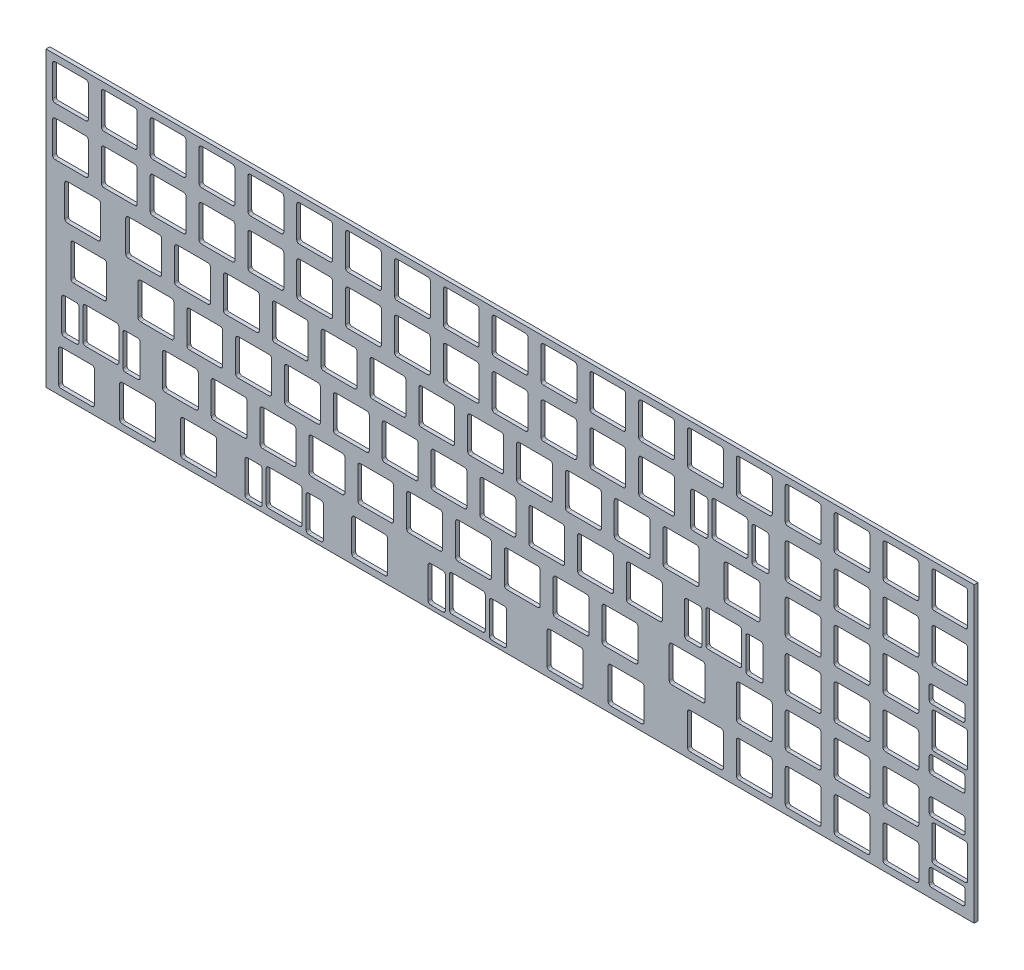
SolidWorks part; units mm, degrees
ref_plane "Front Plane" through (0, 0, 0) normal (0, 0, 1) x (1, 0, 0)
ref_plane "Top Plane" through (0, 0, 0) normal (0, 1, 0) x (1, 0, 0)
ref_plane "Right Plane" through (0, 0, 0) normal (1, 0, 0) x (0, 0, -1)
sketch "Model" plane through (0, 0, 0) normal (0, 0, 1) x (1, 0, 0)
  line L0 (3.525, -2.525) -> (15.525, -2.525)
  line L1 (3.525, -16.525) -> (15.525, -16.525)
  line L2 (2.525, -3.525) -> (2.525, -15.525)
  line L3 (16.525, -3.525) -> (16.525, -15.525)
  line L4 (22.575, -2.525) -> (34.575, -2.525)
  line L5 (22.575, -16.525) -> (34.575, -16.525)
  line L6 (21.575, -3.525) -> (21.575, -15.525)
  line L7 (35.575, -3.525) -> (35.575, -15.525)
  line L8 (41.625, -2.525) -> (53.625, -2.525)
  line L9 (41.625, -16.525) -> (53.625, -16.525)
  line L10 (40.625, -3.525) -> (40.625, -15.525)
  line L11 (54.625, -3.525) -> (54.625, -15.525)
  line L12 (60.675, -2.525) -> (72.675, -2.525)
  line L13 (60.675, -16.525) -> (72.675, -16.525)
  line L14 (59.675, -3.525) -> (59.675, -15.525)
  line L15 (73.675, -3.525) -> (73.675, -15.525)
  line L16 (79.725, -2.525) -> (91.725, -2.525)
  line L17 (79.725, -16.525) -> (91.725, -16.525)
  line L18 (78.725, -3.525) -> (78.725, -15.525)
  line L19 (92.725, -3.525) -> (92.725, -15.525)
  line L20 (98.775, -2.525) -> (110.775, -2.525)
  line L21 (98.775, -16.525) -> (110.775, -16.525)
  line L22 (97.775, -3.525) -> (97.775, -15.525)
  line L23 (111.775, -3.525) -> (111.775, -15.525)
  line L24 (117.825, -2.525) -> (129.825, -2.525)
  line L25 (117.825, -16.525) -> (129.825, -16.525)
  line L26 (116.825, -3.525) -> (116.825, -15.525)
  line L27 (130.825, -3.525) -> (130.825, -15.525)
  line L28 (136.875, -2.525) -> (148.875, -2.525)
  line L29 (136.875, -16.525) -> (148.875, -16.525)
  line L30 (135.875, -3.525) -> (135.875, -15.525)
  line L31 (149.875, -3.525) -> (149.875, -15.525)
  line L32 (155.925, -2.525) -> (167.925, -2.525)
  line L33 (155.925, -16.525) -> (167.925, -16.525)
  line L34 (154.925, -3.525) -> (154.925, -15.525)
  line L35 (168.925, -3.525) -> (168.925, -15.525)
  line L36 (174.975, -2.525) -> (186.975, -2.525)
  line L37 (174.975, -16.525) -> (186.975, -16.525)
  line L38 (173.975, -3.525) -> (173.975, -15.525)
  line L39 (187.975, -3.525) -> (187.975, -15.525)
  line L40 (194.025, -2.525) -> (206.025, -2.525)
  line L41 (194.025, -16.525) -> (206.025, -16.525)
  line L42 (193.025, -3.525) -> (193.025, -15.525)
  line L43 (207.025, -3.525) -> (207.025, -15.525)
  line L44 (213.075, -2.525) -> (225.075, -2.525)
  line L45 (213.075, -16.525) -> (225.075, -16.525)
  line L46 (212.075, -3.525) -> (212.075, -15.525)
  line L47 (226.075, -3.525) -> (226.075, -15.525)
  line L48 (232.125, -2.525) -> (244.125, -2.525)
  line L49 (232.125, -16.525) -> (244.125, -16.525)
  line L50 (231.125, -3.525) -> (231.125, -15.525)
  line L51 (245.125, -3.525) -> (245.125, -15.525)
  line L52 (251.175, -2.525) -> (263.175, -2.525)
  line L53 (251.175, -16.525) -> (263.175, -16.525)
  line L54 (250.175, -3.525) -> (250.175, -15.525)
  line L55 (264.175, -3.525) -> (264.175, -15.525)
  line L56 (270.225, -2.525) -> (282.225, -2.525)
  line L57 (270.225, -16.525) -> (282.225, -16.525)
  line L58 (269.225, -3.525) -> (269.225, -15.525)
  line L59 (283.225, -3.525) -> (283.225, -15.525)
  line L60 (289.275, -2.525) -> (301.275, -2.525)
  line L61 (289.275, -16.525) -> (301.275, -16.525)
  line L62 (288.275, -3.525) -> (288.275, -15.525)
  line L63 (302.275, -3.525) -> (302.275, -15.525)
  line L64 (308.325, -2.525) -> (320.325, -2.525)
  line L65 (308.325, -16.525) -> (320.325, -16.525)
  line L66 (307.325, -3.525) -> (307.325, -15.525)
  line L67 (321.325, -3.525) -> (321.325, -15.525)
  line L68 (327.375, -2.525) -> (339.375, -2.525)
  line L69 (327.375, -16.525) -> (339.375, -16.525)
  line L70 (326.375, -3.525) -> (326.375, -15.525)
  line L71 (340.375, -3.525) -> (340.375, -15.525)
  line L72 (346.425, -2.525) -> (358.425, -2.525)
  line L73 (346.425, -16.525) -> (358.425, -16.525)
  line L74 (345.425, -3.525) -> (345.425, -15.525)
  line L75 (359.425, -3.525) -> (359.425, -15.525)
  line L76 (3.525, -21.575) -> (15.525, -21.575)
  line L77 (3.525, -35.575) -> (15.525, -35.575)
  line L78 (2.525, -22.575) -> (2.525, -34.575)
  line L79 (16.525, -22.575) -> (16.525, -34.575)
  line L80 (22.575, -21.575) -> (34.575, -21.575)
  line L81 (22.575, -35.575) -> (34.575, -35.575)
  line L82 (21.575, -22.575) -> (21.575, -34.575)
  line L83 (35.575, -22.575) -> (35.575, -34.575)
  line L84 (41.625, -21.575) -> (53.625, -21.575)
  line L85 (41.625, -35.575) -> (53.625, -35.575)
  line L86 (40.625, -22.575) -> (40.625, -34.575)
  line L87 (54.625, -22.575) -> (54.625, -34.575)
  line L88 (60.675, -21.575) -> (72.675, -21.575)
  line L89 (60.675, -35.575) -> (72.675, -35.575)
  line L90 (59.675, -22.575) -> (59.675, -34.575)
  line L91 (73.675, -22.575) -> (73.675, -34.575)
  line L92 (79.725, -21.575) -> (91.725, -21.575)
  line L93 (79.725, -35.575) -> (91.725, -35.575)
  line L94 (78.725, -22.575) -> (78.725, -34.575)
  line L95 (92.725, -22.575) -> (92.725, -34.575)
  line L96 (98.775, -21.575) -> (110.775, -21.575)
  line L97 (98.775, -35.575) -> (110.775, -35.575)
  line L98 (97.775, -22.575) -> (97.775, -34.575)
  line L99 (111.775, -22.575) -> (111.775, -34.575)
  line L100 (117.825, -21.575) -> (129.825, -21.575)
  line L101 (117.825, -35.575) -> (129.825, -35.575)
  line L102 (116.825, -22.575) -> (116.825, -34.575)
  line L103 (130.825, -22.575) -> (130.825, -34.575)
  line L104 (136.875, -21.575) -> (148.875, -21.575)
  line L105 (136.875, -35.575) -> (148.875, -35.575)
  line L106 (135.875, -22.575) -> (135.875, -34.575)
  line L107 (149.875, -22.575) -> (149.875, -34.575)
  line L108 (155.925, -21.575) -> (167.925, -21.575)
  line L109 (155.925, -35.575) -> (167.925, -35.575)
  line L110 (154.925, -22.575) -> (154.925, -34.575)
  line L111 (168.925, -22.575) -> (168.925, -34.575)
  line L112 (174.975, -21.575) -> (186.975, -21.575)
  line L113 (174.975, -35.575) -> (186.975, -35.575)
  line L114 (173.975, -22.575) -> (173.975, -34.575)
  line L115 (187.975, -22.575) -> (187.975, -34.575)
  line L116 (194.025, -21.575) -> (206.025, -21.575)
  line L117 (194.025, -35.575) -> (206.025, -35.575)
  line L118 (193.025, -22.575) -> (193.025, -34.575)
  line L119 (207.025, -22.575) -> (207.025, -34.575)
  line L120 (213.075, -21.575) -> (225.075, -21.575)
  line L121 (213.075, -35.575) -> (225.075, -35.575)
  line L122 (212.075, -22.575) -> (212.075, -34.575)
  line L123 (226.075, -22.575) -> (226.075, -34.575)
  line L124 (232.125, -21.575) -> (244.125, -21.575)
  line L125 (232.125, -35.575) -> (244.125, -35.575)
  line L126 (231.125, -22.575) -> (231.125, -34.575)
  line L127 (245.125, -22.575) -> (245.125, -34.575)
  line L128 (260.7, -21.575) -> (272.7, -21.575)
  line L129 (260.7, -35.575) -> (272.7, -35.575)
  line L130 (259.7, -22.575) -> (259.7, -34.575)
  line L131 (273.7, -22.575) -> (273.7, -34.575)
  line L132 (276.263, -22.575) -> (281.013, -22.575)
  line L133 (276.263, -36.575) -> (281.013, -36.575)
  line L134 (275.263, -23.575) -> (275.263, -35.575)
  line L135 (282.013, -23.575) -> (282.013, -35.575)
  line L136 (252.387, -22.575) -> (257.137, -22.575)
  line L137 (252.387, -36.575) -> (257.137, -36.575)
  line L138 (251.387, -23.575) -> (251.387, -35.575)
  line L139 (258.137, -23.575) -> (258.137, -35.575)
  line L140 (289.275, -21.575) -> (301.275, -21.575)
  line L141 (289.275, -35.575) -> (301.275, -35.575)
  line L142 (288.275, -22.575) -> (288.275, -34.575)
  line L143 (302.275, -22.575) -> (302.275, -34.575)
  line L144 (308.325, -21.575) -> (320.325, -21.575)
  line L145 (308.325, -35.575) -> (320.325, -35.575)
  line L146 (307.325, -22.575) -> (307.325, -34.575)
  line L147 (321.325, -22.575) -> (321.325, -34.575)
  line L148 (327.375, -21.575) -> (339.375, -21.575)
  line L149 (327.375, -35.575) -> (339.375, -35.575)
  line L150 (326.375, -22.575) -> (326.375, -34.575)
  line L151 (340.375, -22.575) -> (340.375, -34.575)
  line L152 (346.425, -21.575) -> (358.425, -21.575)
  line L153 (346.425, -35.575) -> (358.425, -35.575)
  line L154 (345.425, -22.575) -> (345.425, -34.575)
  line L155 (359.425, -22.575) -> (359.425, -34.575)
  line L156 (8.2875, -40.625) -> (20.2875, -40.625)
  line L157 (8.2875, -54.625) -> (20.2875, -54.625)
  line L158 (7.2875, -41.625) -> (7.2875, -53.625)
  line L159 (21.2875, -41.625) -> (21.2875, -53.625)
  line L160 (32.1, -40.625) -> (44.1, -40.625)
  line L161 (32.1, -54.625) -> (44.1, -54.625)
  line L162 (31.1, -41.625) -> (31.1, -53.625)
  line L163 (45.1, -41.625) -> (45.1, -53.625)
  line L164 (51.15, -40.625) -> (63.15, -40.625)
  line L165 (51.15, -54.625) -> (63.15, -54.625)
  line L166 (50.15, -41.625) -> (50.15, -53.625)
  line L167 (64.15, -41.625) -> (64.15, -53.625)
  line L168 (70.2, -40.625) -> (82.2, -40.625)
  line L169 (70.2, -54.625) -> (82.2, -54.625)
  line L170 (69.2, -41.625) -> (69.2, -53.625)
  line L171 (83.2, -41.625) -> (83.2, -53.625)
  line L172 (89.25, -40.625) -> (101.25, -40.625)
  line L173 (89.25, -54.625) -> (101.25, -54.625)
  line L174 (88.25, -41.625) -> (88.25, -53.625)
  line L175 (102.25, -41.625) -> (102.25, -53.625)
  line L176 (108.3, -40.625) -> (120.3, -40.625)
  line L177 (108.3, -54.625) -> (120.3, -54.625)
  line L178 (107.3, -41.625) -> (107.3, -53.625)
  line L179 (121.3, -41.625) -> (121.3, -53.625)
  line L180 (127.35, -40.625) -> (139.35, -40.625)
  line L181 (127.35, -54.625) -> (139.35, -54.625)
  line L182 (126.35, -41.625) -> (126.35, -53.625)
  line L183 (140.35, -41.625) -> (140.35, -53.625)
  line L184 (146.4, -40.625) -> (158.4, -40.625)
  line L185 (146.4, -54.625) -> (158.4, -54.625)
  line L186 (145.4, -41.625) -> (145.4, -53.625)
  line L187 (159.4, -41.625) -> (159.4, -53.625)
  line L188 (165.45, -40.625) -> (177.45, -40.625)
  line L189 (165.45, -54.625) -> (177.45, -54.625)
  line L190 (164.45, -41.625) -> (164.45, -53.625)
  line L191 (178.45, -41.625) -> (178.45, -53.625)
  line L192 (184.5, -40.625) -> (196.5, -40.625)
  line L193 (184.5, -54.625) -> (196.5, -54.625)
  line L194 (183.5, -41.625) -> (183.5, -53.625)
  line L195 (197.5, -41.625) -> (197.5, -53.625)
  line L196 (203.55, -40.625) -> (215.55, -40.625)
  line L197 (203.55, -54.625) -> (215.55, -54.625)
  line L198 (202.55, -41.625) -> (202.55, -53.625)
  line L199 (216.55, -41.625) -> (216.55, -53.625)
  line L200 (222.6, -40.625) -> (234.6, -40.625)
  line L201 (222.6, -54.625) -> (234.6, -54.625)
  line L202 (221.6, -41.625) -> (221.6, -53.625)
  line L203 (235.6, -41.625) -> (235.6, -53.625)
  line L204 (241.65, -40.625) -> (253.65, -40.625)
  line L205 (241.65, -54.625) -> (253.65, -54.625)
  line L206 (240.65, -41.625) -> (240.65, -53.625)
  line L207 (254.65, -41.625) -> (254.65, -53.625)
  line L208 (265.4625, -40.625) -> (277.4625, -40.625)
  line L209 (265.4625, -54.625) -> (277.4625, -54.625)
  line L210 (264.4625, -41.625) -> (264.4625, -53.625)
  line L211 (278.4625, -41.625) -> (278.4625, -53.625)
  line L212 (289.275, -40.625) -> (301.275, -40.625)
  line L213 (289.275, -54.625) -> (301.275, -54.625)
  line L214 (288.275, -41.625) -> (288.275, -53.625)
  line L215 (302.275, -41.625) -> (302.275, -53.625)
  line L216 (308.325, -40.625) -> (320.325, -40.625)
  line L217 (308.325, -54.625) -> (320.325, -54.625)
  line L218 (307.325, -41.625) -> (307.325, -53.625)
  line L219 (321.325, -41.625) -> (321.325, -53.625)
  line L220 (327.375, -40.625) -> (339.375, -40.625)
  line L221 (327.375, -54.625) -> (339.375, -54.625)
  line L222 (326.375, -41.625) -> (326.375, -53.625)
  line L223 (340.375, -41.625) -> (340.375, -53.625)
  line L224 (359.425, -51.15) -> (359.425, -63.15)
  line L225 (345.425, -51.15) -> (345.425, -63.15)
  line L226 (358.425, -50.15) -> (346.425, -50.15)
  line L227 (358.425, -64.15) -> (346.425, -64.15)
  line L228 (358.425, -66.713) -> (358.425, -71.463)
  line L229 (344.425, -66.713) -> (344.425, -71.463)
  line L230 (357.425, -65.713) -> (345.425, -65.713)
  line L231 (357.425, -72.463) -> (345.425, -72.463)
  line L232 (358.425, -42.837) -> (358.425, -47.587)
  line L233 (344.425, -42.837) -> (344.425, -47.587)
  line L234 (357.425, -41.837) -> (345.425, -41.837)
  line L235 (357.425, -48.587) -> (345.425, -48.587)
  line L236 (10.6688, -59.675) -> (22.6688, -59.675)
  line L237 (10.6688, -73.675) -> (22.6688, -73.675)
  line L238 (9.6688, -60.675) -> (9.6688, -72.675)
  line L239 (23.6688, -60.675) -> (23.6688, -72.675)
  line L240 (36.8625, -59.675) -> (48.8625, -59.675)
  line L241 (36.8625, -73.675) -> (48.8625, -73.675)
  line L242 (35.8625, -60.675) -> (35.8625, -72.675)
  line L243 (49.8625, -60.675) -> (49.8625, -72.675)
  line L244 (55.9125, -59.675) -> (67.9125, -59.675)
  line L245 (55.9125, -73.675) -> (67.9125, -73.675)
  line L246 (54.9125, -60.675) -> (54.9125, -72.675)
  line L247 (68.9125, -60.675) -> (68.9125, -72.675)
  line L248 (74.9625, -59.675) -> (86.9625, -59.675)
  line L249 (74.9625, -73.675) -> (86.9625, -73.675)
  line L250 (73.9625, -60.675) -> (73.9625, -72.675)
  line L251 (87.9625, -60.675) -> (87.9625, -72.675)
  line L252 (94.0125, -59.675) -> (106.0125, -59.675)
  line L253 (94.0125, -73.675) -> (106.0125, -73.675)
  line L254 (93.0125, -60.675) -> (93.0125, -72.675)
  line L255 (107.0125, -60.675) -> (107.0125, -72.675)
  line L256 (113.0625, -59.675) -> (125.0625, -59.675)
  line L257 (113.0625, -73.675) -> (125.0625, -73.675)
  line L258 (112.0625, -60.675) -> (112.0625, -72.675)
  line L259 (126.0625, -60.675) -> (126.0625, -72.675)
  line L260 (132.1125, -59.675) -> (144.1125, -59.675)
  line L261 (132.1125, -73.675) -> (144.1125, -73.675)
  line L262 (131.1125, -60.675) -> (131.1125, -72.675)
  line L263 (145.1125, -60.675) -> (145.1125, -72.675)
  line L264 (151.1625, -59.675) -> (163.1625, -59.675)
  line L265 (151.1625, -73.675) -> (163.1625, -73.675)
  line L266 (150.1625, -60.675) -> (150.1625, -72.675)
  line L267 (164.1625, -60.675) -> (164.1625, -72.675)
  line L268 (170.2125, -59.675) -> (182.2125, -59.675)
  line L269 (170.2125, -73.675) -> (182.2125, -73.675)
  line L270 (169.2125, -60.675) -> (169.2125, -72.675)
  line L271 (183.2125, -60.675) -> (183.2125, -72.675)
  line L272 (189.2625, -59.675) -> (201.2625, -59.675)
  line L273 (189.2625, -73.675) -> (201.2625, -73.675)
  line L274 (188.2625, -60.675) -> (188.2625, -72.675)
  line L275 (202.2625, -60.675) -> (202.2625, -72.675)
  line L276 (208.3125, -59.675) -> (220.3125, -59.675)
  line L277 (208.3125, -73.675) -> (220.3125, -73.675)
  line L278 (207.3125, -60.675) -> (207.3125, -72.675)
  line L279 (221.3125, -60.675) -> (221.3125, -72.675)
  line L280 (227.3625, -59.675) -> (239.3625, -59.675)
  line L281 (227.3625, -73.675) -> (239.3625, -73.675)
  line L282 (226.3625, -60.675) -> (226.3625, -72.675)
  line L283 (240.3625, -60.675) -> (240.3625, -72.675)
  line L284 (258.3188, -59.675) -> (270.3188, -59.675)
  line L285 (258.3188, -73.675) -> (270.3188, -73.675)
  line L286 (257.3188, -60.675) -> (257.3188, -72.675)
  line L287 (271.3188, -60.675) -> (271.3188, -72.675)
  line L288 (273.8818, -60.675) -> (278.6318, -60.675)
  line L289 (273.8818, -74.675) -> (278.6318, -74.675)
  line L290 (272.8818, -61.675) -> (272.8818, -73.675)
  line L291 (279.6318, -61.675) -> (279.6318, -73.675)
  line L292 (250.0058, -60.675) -> (254.7558, -60.675)
  line L293 (250.0058, -74.675) -> (254.7558, -74.675)
  line L294 (249.0058, -61.675) -> (249.0058, -73.675)
  line L295 (255.7558, -61.675) -> (255.7558, -73.675)
  line L296 (289.275, -59.675) -> (301.275, -59.675)
  line L297 (289.275, -73.675) -> (301.275, -73.675)
  line L298 (288.275, -60.675) -> (288.275, -72.675)
  line L299 (302.275, -60.675) -> (302.275, -72.675)
  line L300 (308.325, -59.675) -> (320.325, -59.675)
  line L301 (308.325, -73.675) -> (320.325, -73.675)
  line L302 (307.325, -60.675) -> (307.325, -72.675)
  line L303 (321.325, -60.675) -> (321.325, -72.675)
  line L304 (327.375, -59.675) -> (339.375, -59.675)
  line L305 (327.375, -73.675) -> (339.375, -73.675)
  line L306 (326.375, -60.675) -> (326.375, -72.675)
  line L307 (340.375, -60.675) -> (340.375, -72.675)
  line L308 (15.4313, -78.725) -> (27.4313, -78.725)
  line L309 (15.4313, -92.725) -> (27.4313, -92.725)
  line L310 (14.4313, -79.725) -> (14.4313, -91.725)
  line L311 (28.4313, -79.725) -> (28.4313, -91.725)
  line L312 (30.9943, -79.725) -> (35.7443, -79.725)
  line L313 (30.9943, -93.725) -> (35.7443, -93.725)
  line L314 (29.9943, -80.725) -> (29.9943, -92.725)
  line L315 (36.7443, -80.725) -> (36.7443, -92.725)
  line L316 (7.1183, -79.725) -> (11.8682, -79.725)
  line L317 (7.1183, -93.725) -> (11.8682, -93.725)
  line L318 (6.1182, -80.725) -> (6.1182, -92.725)
  line L319 (12.8683, -80.725) -> (12.8683, -92.725)
  line L320 (46.3875, -78.725) -> (58.3875, -78.725)
  line L321 (46.3875, -92.725) -> (58.3875, -92.725)
  line L322 (45.3875, -79.725) -> (45.3875, -91.725)
  line L323 (59.3875, -79.725) -> (59.3875, -91.725)
  line L324 (65.4375, -78.725) -> (77.4375, -78.725)
  line L325 (65.4375, -92.725) -> (77.4375, -92.725)
  line L326 (64.4375, -79.725) -> (64.4375, -91.725)
  line L327 (78.4375, -79.725) -> (78.4375, -91.725)
  line L328 (84.4875, -78.725) -> (96.4875, -78.725)
  line L329 (84.4875, -92.725) -> (96.4875, -92.725)
  line L330 (83.4875, -79.725) -> (83.4875, -91.725)
  line L331 (97.4875, -79.725) -> (97.4875, -91.725)
  line L332 (103.5375, -78.725) -> (115.5375, -78.725)
  line L333 (103.5375, -92.725) -> (115.5375, -92.725)
  line L334 (102.5375, -79.725) -> (102.5375, -91.725)
  line L335 (116.5375, -79.725) -> (116.5375, -91.725)
  line L336 (122.5875, -78.725) -> (134.5875, -78.725)
  line L337 (122.5875, -92.725) -> (134.5875, -92.725)
  line L338 (121.5875, -79.725) -> (121.5875, -91.725)
  line L339 (135.5875, -79.725) -> (135.5875, -91.725)
  line L340 (141.6375, -78.725) -> (153.6375, -78.725)
  line L341 (141.6375, -92.725) -> (153.6375, -92.725)
  line L342 (140.6375, -79.725) -> (140.6375, -91.725)
  line L343 (154.6375, -79.725) -> (154.6375, -91.725)
  line L344 (160.6875, -78.725) -> (172.6875, -78.725)
  line L345 (160.6875, -92.725) -> (172.6875, -92.725)
  line L346 (159.6875, -79.725) -> (159.6875, -91.725)
  line L347 (173.6875, -79.725) -> (173.6875, -91.725)
  line L348 (179.7375, -78.725) -> (191.7375, -78.725)
  line L349 (179.7375, -92.725) -> (191.7375, -92.725)
  line L350 (178.7375, -79.725) -> (178.7375, -91.725)
  line L351 (192.7375, -79.725) -> (192.7375, -91.725)
  line L352 (198.7875, -78.725) -> (210.7875, -78.725)
  line L353 (198.7875, -92.725) -> (210.7875, -92.725)
  line L354 (197.7875, -79.725) -> (197.7875, -91.725)
  line L355 (211.7875, -79.725) -> (211.7875, -91.725)
  line L356 (217.8375, -78.725) -> (229.8375, -78.725)
  line L357 (217.8375, -92.725) -> (229.8375, -92.725)
  line L358 (216.8375, -79.725) -> (216.8375, -91.725)
  line L359 (230.8375, -79.725) -> (230.8375, -91.725)
  line L360 (244.0313, -78.725) -> (256.0313, -78.725)
  line L361 (244.0313, -92.725) -> (256.0313, -92.725)
  line L362 (243.0313, -79.725) -> (243.0313, -91.725)
  line L363 (257.0313, -79.725) -> (257.0313, -91.725)
  line L364 (270.225, -78.725) -> (282.225, -78.725)
  line L365 (270.225, -92.725) -> (282.225, -92.725)
  line L366 (269.225, -79.725) -> (269.225, -91.725)
  line L367 (283.225, -79.725) -> (283.225, -91.725)
  line L368 (289.275, -78.725) -> (301.275, -78.725)
  line L369 (289.275, -92.725) -> (301.275, -92.725)
  line L370 (288.275, -79.725) -> (288.275, -91.725)
  line L371 (302.275, -79.725) -> (302.275, -91.725)
  line L372 (308.325, -78.725) -> (320.325, -78.725)
  line L373 (308.325, -92.725) -> (320.325, -92.725)
  line L374 (307.325, -79.725) -> (307.325, -91.725)
  line L375 (321.325, -79.725) -> (321.325, -91.725)
  line L376 (327.375, -78.725) -> (339.375, -78.725)
  line L377 (327.375, -92.725) -> (339.375, -92.725)
  line L378 (326.375, -79.725) -> (326.375, -91.725)
  line L379 (340.375, -79.725) -> (340.375, -91.725)
  line L380 (359.425, -89.25) -> (359.425, -101.25)
  line L381 (345.425, -89.25) -> (345.425, -101.25)
  line L382 (358.425, -88.25) -> (346.425, -88.25)
  line L383 (358.425, -102.25) -> (346.425, -102.25)
  line L384 (358.425, -104.813) -> (358.425, -109.563)
  line L385 (344.425, -104.813) -> (344.425, -109.563)
  line L386 (357.425, -103.813) -> (345.425, -103.813)
  line L387 (357.425, -110.563) -> (345.425, -110.563)
  line L388 (358.425, -80.937) -> (358.425, -85.687)
  line L389 (344.425, -80.937) -> (344.425, -85.687)
  line L390 (357.425, -79.937) -> (345.425, -79.937)
  line L391 (357.425, -86.687) -> (345.425, -86.687)
  line L392 (5.9063, -97.775) -> (17.9063, -97.775)
  line L393 (5.9063, -111.775) -> (17.9063, -111.775)
  line L394 (4.9063, -98.775) -> (4.9063, -110.775)
  line L395 (18.9063, -98.775) -> (18.9063, -110.775)
  line L396 (29.7188, -97.775) -> (41.7188, -97.775)
  line L397 (29.7188, -111.775) -> (41.7188, -111.775)
  line L398 (28.7188, -98.775) -> (28.7188, -110.775)
  line L399 (42.7188, -98.775) -> (42.7188, -110.775)
  line L400 (53.5312, -97.775) -> (65.5312, -97.775)
  line L401 (53.5312, -111.775) -> (65.5312, -111.775)
  line L402 (52.5313, -98.775) -> (52.5313, -110.775)
  line L403 (66.5313, -98.775) -> (66.5313, -110.775)
  line L404 (86.8688, -97.775) -> (98.8688, -97.775)
  line L405 (86.8688, -111.775) -> (98.8688, -111.775)
  line L406 (85.8688, -98.775) -> (85.8688, -110.775)
  line L407 (99.8688, -98.775) -> (99.8688, -110.775)
  line L408 (102.4318, -98.775) -> (107.1818, -98.775)
  line L409 (102.4318, -112.775) -> (107.1818, -112.775)
  line L410 (101.4318, -99.775) -> (101.4318, -111.775)
  line L411 (108.1818, -99.775) -> (108.1818, -111.775)
  line L412 (78.5558, -98.775) -> (83.3058, -98.775)
  line L413 (78.5558, -112.775) -> (83.3058, -112.775)
  line L414 (77.5558, -99.775) -> (77.5558, -111.775)
  line L415 (84.3058, -99.775) -> (84.3058, -111.775)
  line L416 (120.2063, -97.775) -> (132.2063, -97.775)
  line L417 (120.2063, -111.775) -> (132.2063, -111.775)
  line L418 (119.2063, -98.775) -> (119.2063, -110.775)
  line L419 (133.2063, -98.775) -> (133.2063, -110.775)
  line L420 (158.3063, -97.775) -> (170.3063, -97.775)
  line L421 (158.3063, -111.775) -> (170.3063, -111.775)
  line L422 (157.3063, -98.775) -> (157.3063, -110.775)
  line L423 (171.3063, -98.775) -> (171.3063, -110.775)
  line L424 (173.8692, -98.775) -> (178.6193, -98.775)
  line L425 (173.8692, -112.775) -> (178.6193, -112.775)
  line L426 (172.8692, -99.775) -> (172.8692, -111.775)
  line L427 (179.6193, -99.775) -> (179.6193, -111.775)
  line L428 (149.9933, -98.775) -> (154.7432, -98.775)
  line L429 (149.9933, -112.775) -> (154.7432, -112.775)
  line L430 (148.9932, -99.775) -> (148.9932, -111.775)
  line L431 (155.7432, -99.775) -> (155.7432, -111.775)
  line L432 (196.4062, -97.775) -> (208.4063, -97.775)
  line L433 (196.4062, -111.775) -> (208.4063, -111.775)
  line L434 (195.4063, -98.775) -> (195.4063, -110.775)
  line L435 (209.4063, -98.775) -> (209.4063, -110.775)
  line L436 (220.2188, -97.775) -> (232.2188, -97.775)
  line L437 (220.2188, -111.775) -> (232.2188, -111.775)
  line L438 (219.2188, -98.775) -> (219.2188, -110.775)
  line L439 (233.2188, -98.775) -> (233.2188, -110.775)
  line L440 (251.175, -97.775) -> (263.175, -97.775)
  line L441 (251.175, -111.775) -> (263.175, -111.775)
  line L442 (250.175, -98.775) -> (250.175, -110.775)
  line L443 (264.175, -98.775) -> (264.175, -110.775)
  line L444 (270.225, -97.775) -> (282.225, -97.775)
  line L445 (270.225, -111.775) -> (282.225, -111.775)
  line L446 (269.225, -98.775) -> (269.225, -110.775)
  line L447 (283.225, -98.775) -> (283.225, -110.775)
  line L448 (289.275, -97.775) -> (301.275, -97.775)
  line L449 (289.275, -111.775) -> (301.275, -111.775)
  line L450 (288.275, -98.775) -> (288.275, -110.775)
  line L451 (302.275, -98.775) -> (302.275, -110.775)
  line L452 (308.325, -97.775) -> (320.325, -97.775)
  line L453 (308.325, -111.775) -> (320.325, -111.775)
  line L454 (307.325, -98.775) -> (307.325, -110.775)
  line L455 (321.325, -98.775) -> (321.325, -110.775)
  line L456 (327.375, -97.775) -> (339.375, -97.775)
  line L457 (327.375, -111.775) -> (339.375, -111.775)
  line L458 (326.375, -98.775) -> (326.375, -110.775)
  line L459 (340.375, -98.775) -> (340.375, -110.775)
  line L460 (0, 0) -> (361.952, 0)
  line L461 (0, -114.3) -> (361.952, -114.3)
  line L462 (0, 0) -> (0, -114.3)
  line L463 (361.952, 0) -> (361.952, -114.3)
  arc A0 (3.525, -2.525) -> (2.525, -3.525) centre (3.525, -3.525) ccw
  arc A1 (16.525, -3.525) -> (15.525, -2.525) centre (15.525, -3.525) ccw
  arc A2 (2.525, -15.525) -> (3.525, -16.525) centre (3.525, -15.525) ccw
  arc A3 (15.525, -16.525) -> (16.525, -15.525) centre (15.525, -15.525) ccw
  arc A4 (22.575, -2.525) -> (21.575, -3.525) centre (22.575, -3.525) ccw
  arc A5 (35.575, -3.525) -> (34.575, -2.525) centre (34.575, -3.525) ccw
  arc A6 (21.575, -15.525) -> (22.575, -16.525) centre (22.575, -15.525) ccw
  arc A7 (34.575, -16.525) -> (35.575, -15.525) centre (34.575, -15.525) ccw
  arc A8 (41.625, -2.525) -> (40.625, -3.525) centre (41.625, -3.525) ccw
  arc A9 (54.625, -3.525) -> (53.625, -2.525) centre (53.625, -3.525) ccw
  arc A10 (40.625, -15.525) -> (41.625, -16.525) centre (41.625, -15.525) ccw
  arc A11 (53.625, -16.525) -> (54.625, -15.525) centre (53.625, -15.525) ccw
  arc A12 (60.675, -2.525) -> (59.675, -3.525) centre (60.675, -3.525) ccw
  arc A13 (73.675, -3.525) -> (72.675, -2.525) centre (72.675, -3.525) ccw
  arc A14 (59.675, -15.525) -> (60.675, -16.525) centre (60.675, -15.525) ccw
  arc A15 (72.675, -16.525) -> (73.675, -15.525) centre (72.675, -15.525) ccw
  arc A16 (79.725, -2.525) -> (78.725, -3.525) centre (79.725, -3.525) ccw
  arc A17 (92.725, -3.525) -> (91.725, -2.525) centre (91.725, -3.525) ccw
  arc A18 (78.725, -15.525) -> (79.725, -16.525) centre (79.725, -15.525) ccw
  arc A19 (91.725, -16.525) -> (92.725, -15.525) centre (91.725, -15.525) ccw
  arc A20 (98.775, -2.525) -> (97.775, -3.525) centre (98.775, -3.525) ccw
  arc A21 (111.775, -3.525) -> (110.775, -2.525) centre (110.775, -3.525) ccw
  arc A22 (97.775, -15.525) -> (98.775, -16.525) centre (98.775, -15.525) ccw
  arc A23 (110.775, -16.525) -> (111.775, -15.525) centre (110.775, -15.525) ccw
  arc A24 (117.825, -2.525) -> (116.825, -3.525) centre (117.825, -3.525) ccw
  arc A25 (130.825, -3.525) -> (129.825, -2.525) centre (129.825, -3.525) ccw
  arc A26 (116.825, -15.525) -> (117.825, -16.525) centre (117.825, -15.525) ccw
  arc A27 (129.825, -16.525) -> (130.825, -15.525) centre (129.825, -15.525) ccw
  arc A28 (136.875, -2.525) -> (135.875, -3.525) centre (136.875, -3.525) ccw
  arc A29 (149.875, -3.525) -> (148.875, -2.525) centre (148.875, -3.525) ccw
  arc A30 (135.875, -15.525) -> (136.875, -16.525) centre (136.875, -15.525) ccw
  arc A31 (148.875, -16.525) -> (149.875, -15.525) centre (148.875, -15.525) ccw
  arc A32 (155.925, -2.525) -> (154.925, -3.525) centre (155.925, -3.525) ccw
  arc A33 (168.925, -3.525) -> (167.925, -2.525) centre (167.925, -3.525) ccw
  arc A34 (154.925, -15.525) -> (155.925, -16.525) centre (155.925, -15.525) ccw
  arc A35 (167.925, -16.525) -> (168.925, -15.525) centre (167.925, -15.525) ccw
  arc A36 (174.975, -2.525) -> (173.975, -3.525) centre (174.975, -3.525) ccw
  arc A37 (187.975, -3.525) -> (186.975, -2.525) centre (186.975, -3.525) ccw
  arc A38 (173.975, -15.525) -> (174.975, -16.525) centre (174.975, -15.525) ccw
  arc A39 (186.975, -16.525) -> (187.975, -15.525) centre (186.975, -15.525) ccw
  arc A40 (194.025, -2.525) -> (193.025, -3.525) centre (194.025, -3.525) ccw
  arc A41 (207.025, -3.525) -> (206.025, -2.525) centre (206.025, -3.525) ccw
  arc A42 (193.025, -15.525) -> (194.025, -16.525) centre (194.025, -15.525) ccw
  arc A43 (206.025, -16.525) -> (207.025, -15.525) centre (206.025, -15.525) ccw
  arc A44 (213.075, -2.525) -> (212.075, -3.525) centre (213.075, -3.525) ccw
  arc A45 (226.075, -3.525) -> (225.075, -2.525) centre (225.075, -3.525) ccw
  arc A46 (212.075, -15.525) -> (213.075, -16.525) centre (213.075, -15.525) ccw
  arc A47 (225.075, -16.525) -> (226.075, -15.525) centre (225.075, -15.525) ccw
  arc A48 (232.125, -2.525) -> (231.125, -3.525) centre (232.125, -3.525) ccw
  arc A49 (245.125, -3.525) -> (244.125, -2.525) centre (244.125, -3.525) ccw
  arc A50 (231.125, -15.525) -> (232.125, -16.525) centre (232.125, -15.525) ccw
  arc A51 (244.125, -16.525) -> (245.125, -15.525) centre (244.125, -15.525) ccw
  arc A52 (251.175, -2.525) -> (250.175, -3.525) centre (251.175, -3.525) ccw
  arc A53 (264.175, -3.525) -> (263.175, -2.525) centre (263.175, -3.525) ccw
  arc A54 (250.175, -15.525) -> (251.175, -16.525) centre (251.175, -15.525) ccw
  arc A55 (263.175, -16.525) -> (264.175, -15.525) centre (263.175, -15.525) ccw
  arc A56 (270.225, -2.525) -> (269.225, -3.525) centre (270.225, -3.525) ccw
  arc A57 (283.225, -3.525) -> (282.225, -2.525) centre (282.225, -3.525) ccw
  arc A58 (269.225, -15.525) -> (270.225, -16.525) centre (270.225, -15.525) ccw
  arc A59 (282.225, -16.525) -> (283.225, -15.525) centre (282.225, -15.525) ccw
  arc A60 (289.275, -2.525) -> (288.275, -3.525) centre (289.275, -3.525) ccw
  arc A61 (302.275, -3.525) -> (301.275, -2.525) centre (301.275, -3.525) ccw
  arc A62 (288.275, -15.525) -> (289.275, -16.525) centre (289.275, -15.525) ccw
  arc A63 (301.275, -16.525) -> (302.275, -15.525) centre (301.275, -15.525) ccw
  arc A64 (308.325, -2.525) -> (307.325, -3.525) centre (308.325, -3.525) ccw
  arc A65 (321.325, -3.525) -> (320.325, -2.525) centre (320.325, -3.525) ccw
  arc A66 (307.325, -15.525) -> (308.325, -16.525) centre (308.325, -15.525) ccw
  arc A67 (320.325, -16.525) -> (321.325, -15.525) centre (320.325, -15.525) ccw
  arc A68 (327.375, -2.525) -> (326.375, -3.525) centre (327.375, -3.525) ccw
  arc A69 (340.375, -3.525) -> (339.375, -2.525) centre (339.375, -3.525) ccw
  arc A70 (326.375, -15.525) -> (327.375, -16.525) centre (327.375, -15.525) ccw
  arc A71 (339.375, -16.525) -> (340.375, -15.525) centre (339.375, -15.525) ccw
  arc A72 (346.425, -2.525) -> (345.425, -3.525) centre (346.425, -3.525) ccw
  arc A73 (359.425, -3.525) -> (358.425, -2.525) centre (358.425, -3.525) ccw
  arc A74 (345.425, -15.525) -> (346.425, -16.525) centre (346.425, -15.525) ccw
  arc A75 (358.425, -16.525) -> (359.425, -15.525) centre (358.425, -15.525) ccw
  arc A76 (3.525, -21.575) -> (2.525, -22.575) centre (3.525, -22.575) ccw
  arc A77 (16.525, -22.575) -> (15.525, -21.575) centre (15.525, -22.575) ccw
  arc A78 (2.525, -34.575) -> (3.525, -35.575) centre (3.525, -34.575) ccw
  arc A79 (15.525, -35.575) -> (16.525, -34.575) centre (15.525, -34.575) ccw
  arc A80 (22.575, -21.575) -> (21.575, -22.575) centre (22.575, -22.575) ccw
  arc A81 (35.575, -22.575) -> (34.575, -21.575) centre (34.575, -22.575) ccw
  arc A82 (21.575, -34.575) -> (22.575, -35.575) centre (22.575, -34.575) ccw
  arc A83 (34.575, -35.575) -> (35.575, -34.575) centre (34.575, -34.575) ccw
  arc A84 (41.625, -21.575) -> (40.625, -22.575) centre (41.625, -22.575) ccw
  arc A85 (54.625, -22.575) -> (53.625, -21.575) centre (53.625, -22.575) ccw
  arc A86 (40.625, -34.575) -> (41.625, -35.575) centre (41.625, -34.575) ccw
  arc A87 (53.625, -35.575) -> (54.625, -34.575) centre (53.625, -34.575) ccw
  arc A88 (60.675, -21.575) -> (59.675, -22.575) centre (60.675, -22.575) ccw
  arc A89 (73.675, -22.575) -> (72.675, -21.575) centre (72.675, -22.575) ccw
  arc A90 (59.675, -34.575) -> (60.675, -35.575) centre (60.675, -34.575) ccw
  arc A91 (72.675, -35.575) -> (73.675, -34.575) centre (72.675, -34.575) ccw
  arc A92 (79.725, -21.575) -> (78.725, -22.575) centre (79.725, -22.575) ccw
  arc A93 (92.725, -22.575) -> (91.725, -21.575) centre (91.725, -22.575) ccw
  arc A94 (78.725, -34.575) -> (79.725, -35.575) centre (79.725, -34.575) ccw
  arc A95 (91.725, -35.575) -> (92.725, -34.575) centre (91.725, -34.575) ccw
  arc A96 (98.775, -21.575) -> (97.775, -22.575) centre (98.775, -22.575) ccw
  arc A97 (111.775, -22.575) -> (110.775, -21.575) centre (110.775, -22.575) ccw
  arc A98 (97.775, -34.575) -> (98.775, -35.575) centre (98.775, -34.575) ccw
  arc A99 (110.775, -35.575) -> (111.775, -34.575) centre (110.775, -34.575) ccw
  arc A100 (117.825, -21.575) -> (116.825, -22.575) centre (117.825, -22.575) ccw
  arc A101 (130.825, -22.575) -> (129.825, -21.575) centre (129.825, -22.575) ccw
  arc A102 (116.825, -34.575) -> (117.825, -35.575) centre (117.825, -34.575) ccw
  arc A103 (129.825, -35.575) -> (130.825, -34.575) centre (129.825, -34.575) ccw
  arc A104 (136.875, -21.575) -> (135.875, -22.575) centre (136.875, -22.575) ccw
  arc A105 (149.875, -22.575) -> (148.875, -21.575) centre (148.875, -22.575) ccw
  arc A106 (135.875, -34.575) -> (136.875, -35.575) centre (136.875, -34.575) ccw
  arc A107 (148.875, -35.575) -> (149.875, -34.575) centre (148.875, -34.575) ccw
  arc A108 (155.925, -21.575) -> (154.925, -22.575) centre (155.925, -22.575) ccw
  arc A109 (168.925, -22.575) -> (167.925, -21.575) centre (167.925, -22.575) ccw
  arc A110 (154.925, -34.575) -> (155.925, -35.575) centre (155.925, -34.575) ccw
  arc A111 (167.925, -35.575) -> (168.925, -34.575) centre (167.925, -34.575) ccw
  arc A112 (174.975, -21.575) -> (173.975, -22.575) centre (174.975, -22.575) ccw
  arc A113 (187.975, -22.575) -> (186.975, -21.575) centre (186.975, -22.575) ccw
  arc A114 (173.975, -34.575) -> (174.975, -35.575) centre (174.975, -34.575) ccw
  arc A115 (186.975, -35.575) -> (187.975, -34.575) centre (186.975, -34.575) ccw
  arc A116 (194.025, -21.575) -> (193.025, -22.575) centre (194.025, -22.575) ccw
  arc A117 (207.025, -22.575) -> (206.025, -21.575) centre (206.025, -22.575) ccw
  arc A118 (193.025, -34.575) -> (194.025, -35.575) centre (194.025, -34.575) ccw
  arc A119 (206.025, -35.575) -> (207.025, -34.575) centre (206.025, -34.575) ccw
  arc A120 (213.075, -21.575) -> (212.075, -22.575) centre (213.075, -22.575) ccw
  arc A121 (226.075, -22.575) -> (225.075, -21.575) centre (225.075, -22.575) ccw
  arc A122 (212.075, -34.575) -> (213.075, -35.575) centre (213.075, -34.575) ccw
  arc A123 (225.075, -35.575) -> (226.075, -34.575) centre (225.075, -34.575) ccw
  arc A124 (232.125, -21.575) -> (231.125, -22.575) centre (232.125, -22.575) ccw
  arc A125 (245.125, -22.575) -> (244.125, -21.575) centre (244.125, -22.575) ccw
  arc A126 (231.125, -34.575) -> (232.125, -35.575) centre (232.125, -34.575) ccw
  arc A127 (244.125, -35.575) -> (245.125, -34.575) centre (244.125, -34.575) ccw
  arc A128 (260.7, -21.575) -> (259.7, -22.575) centre (260.7, -22.575) ccw
  arc A129 (273.7, -22.575) -> (272.7, -21.575) centre (272.7, -22.575) ccw
  arc A130 (259.7, -34.575) -> (260.7, -35.575) centre (260.7, -34.575) ccw
  arc A131 (272.7, -35.575) -> (273.7, -34.575) centre (272.7, -34.575) ccw
  arc A132 (276.263, -22.575) -> (275.263, -23.575) centre (276.263, -23.575) ccw
  arc A133 (282.013, -23.575) -> (281.013, -22.575) centre (281.013, -23.575) ccw
  arc A134 (275.263, -35.575) -> (276.263, -36.575) centre (276.263, -35.575) ccw
  arc A135 (281.013, -36.575) -> (282.013, -35.575) centre (281.013, -35.575) ccw
  arc A136 (252.387, -22.575) -> (251.387, -23.575) centre (252.387, -23.575) ccw
  arc A137 (258.137, -23.575) -> (257.137, -22.575) centre (257.137, -23.575) ccw
  arc A138 (251.387, -35.575) -> (252.387, -36.575) centre (252.387, -35.575) ccw
  arc A139 (257.137, -36.575) -> (258.137, -35.575) centre (257.137, -35.575) ccw
  arc A140 (289.275, -21.575) -> (288.275, -22.575) centre (289.275, -22.575) ccw
  arc A141 (302.275, -22.575) -> (301.275, -21.575) centre (301.275, -22.575) ccw
  arc A142 (288.275, -34.575) -> (289.275, -35.575) centre (289.275, -34.575) ccw
  arc A143 (301.275, -35.575) -> (302.275, -34.575) centre (301.275, -34.575) ccw
  arc A144 (308.325, -21.575) -> (307.325, -22.575) centre (308.325, -22.575) ccw
  arc A145 (321.325, -22.575) -> (320.325, -21.575) centre (320.325, -22.575) ccw
  arc A146 (307.325, -34.575) -> (308.325, -35.575) centre (308.325, -34.575) ccw
  arc A147 (320.325, -35.575) -> (321.325, -34.575) centre (320.325, -34.575) ccw
  arc A148 (327.375, -21.575) -> (326.375, -22.575) centre (327.375, -22.575) ccw
  arc A149 (340.375, -22.575) -> (339.375, -21.575) centre (339.375, -22.575) ccw
  arc A150 (326.375, -34.575) -> (327.375, -35.575) centre (327.375, -34.575) ccw
  arc A151 (339.375, -35.575) -> (340.375, -34.575) centre (339.375, -34.575) ccw
  arc A152 (346.425, -21.575) -> (345.425, -22.575) centre (346.425, -22.575) ccw
  arc A153 (359.425, -22.575) -> (358.425, -21.575) centre (358.425, -22.575) ccw
  arc A154 (345.425, -34.575) -> (346.425, -35.575) centre (346.425, -34.575) ccw
  arc A155 (358.425, -35.575) -> (359.425, -34.575) centre (358.425, -34.575) ccw
  arc A156 (8.2875, -40.625) -> (7.2875, -41.625) centre (8.2875, -41.625) ccw
  arc A157 (21.2875, -41.625) -> (20.2875, -40.625) centre (20.2875, -41.625) ccw
  arc A158 (7.2875, -53.625) -> (8.2875, -54.625) centre (8.2875, -53.625) ccw
  arc A159 (20.2875, -54.625) -> (21.2875, -53.625) centre (20.2875, -53.625) ccw
  arc A160 (32.1, -40.625) -> (31.1, -41.625) centre (32.1, -41.625) ccw
  arc A161 (45.1, -41.625) -> (44.1, -40.625) centre (44.1, -41.625) ccw
  arc A162 (31.1, -53.625) -> (32.1, -54.625) centre (32.1, -53.625) ccw
  arc A163 (44.1, -54.625) -> (45.1, -53.625) centre (44.1, -53.625) ccw
  arc A164 (51.15, -40.625) -> (50.15, -41.625) centre (51.15, -41.625) ccw
  arc A165 (64.15, -41.625) -> (63.15, -40.625) centre (63.15, -41.625) ccw
  arc A166 (50.15, -53.625) -> (51.15, -54.625) centre (51.15, -53.625) ccw
  arc A167 (63.15, -54.625) -> (64.15, -53.625) centre (63.15, -53.625) ccw
  arc A168 (70.2, -40.625) -> (69.2, -41.625) centre (70.2, -41.625) ccw
  arc A169 (83.2, -41.625) -> (82.2, -40.625) centre (82.2, -41.625) ccw
  arc A170 (69.2, -53.625) -> (70.2, -54.625) centre (70.2, -53.625) ccw
  arc A171 (82.2, -54.625) -> (83.2, -53.625) centre (82.2, -53.625) ccw
  arc A172 (89.25, -40.625) -> (88.25, -41.625) centre (89.25, -41.625) ccw
  arc A173 (102.25, -41.625) -> (101.25, -40.625) centre (101.25, -41.625) ccw
  arc A174 (88.25, -53.625) -> (89.25, -54.625) centre (89.25, -53.625) ccw
  arc A175 (101.25, -54.625) -> (102.25, -53.625) centre (101.25, -53.625) ccw
  arc A176 (108.3, -40.625) -> (107.3, -41.625) centre (108.3, -41.625) ccw
  arc A177 (121.3, -41.625) -> (120.3, -40.625) centre (120.3, -41.625) ccw
  arc A178 (107.3, -53.625) -> (108.3, -54.625) centre (108.3, -53.625) ccw
  arc A179 (120.3, -54.625) -> (121.3, -53.625) centre (120.3, -53.625) ccw
  arc A180 (127.35, -40.625) -> (126.35, -41.625) centre (127.35, -41.625) ccw
  arc A181 (140.35, -41.625) -> (139.35, -40.625) centre (139.35, -41.625) ccw
  arc A182 (126.35, -53.625) -> (127.35, -54.625) centre (127.35, -53.625) ccw
  arc A183 (139.35, -54.625) -> (140.35, -53.625) centre (139.35, -53.625) ccw
  arc A184 (146.4, -40.625) -> (145.4, -41.625) centre (146.4, -41.625) ccw
  arc A185 (159.4, -41.625) -> (158.4, -40.625) centre (158.4, -41.625) ccw
  arc A186 (145.4, -53.625) -> (146.4, -54.625) centre (146.4, -53.625) ccw
  arc A187 (158.4, -54.625) -> (159.4, -53.625) centre (158.4, -53.625) ccw
  arc A188 (165.45, -40.625) -> (164.45, -41.625) centre (165.45, -41.625) ccw
  arc A189 (178.45, -41.625) -> (177.45, -40.625) centre (177.45, -41.625) ccw
  arc A190 (164.45, -53.625) -> (165.45, -54.625) centre (165.45, -53.625) ccw
  arc A191 (177.45, -54.625) -> (178.45, -53.625) centre (177.45, -53.625) ccw
  arc A192 (184.5, -40.625) -> (183.5, -41.625) centre (184.5, -41.625) ccw
  arc A193 (197.5, -41.625) -> (196.5, -40.625) centre (196.5, -41.625) ccw
  arc A194 (183.5, -53.625) -> (184.5, -54.625) centre (184.5, -53.625) ccw
  arc A195 (196.5, -54.625) -> (197.5, -53.625) centre (196.5, -53.625) ccw
  arc A196 (203.55, -40.625) -> (202.55, -41.625) centre (203.55, -41.625) ccw
  arc A197 (216.55, -41.625) -> (215.55, -40.625) centre (215.55, -41.625) ccw
  arc A198 (202.55, -53.625) -> (203.55, -54.625) centre (203.55, -53.625) ccw
  arc A199 (215.55, -54.625) -> (216.55, -53.625) centre (215.55, -53.625) ccw
  arc A200 (222.6, -40.625) -> (221.6, -41.625) centre (222.6, -41.625) ccw
  arc A201 (235.6, -41.625) -> (234.6, -40.625) centre (234.6, -41.625) ccw
  arc A202 (221.6, -53.625) -> (222.6, -54.625) centre (222.6, -53.625) ccw
  arc A203 (234.6, -54.625) -> (235.6, -53.625) centre (234.6, -53.625) ccw
  arc A204 (241.65, -40.625) -> (240.65, -41.625) centre (241.65, -41.625) ccw
  arc A205 (254.65, -41.625) -> (253.65, -40.625) centre (253.65, -41.625) ccw
  arc A206 (240.65, -53.625) -> (241.65, -54.625) centre (241.65, -53.625) ccw
  arc A207 (253.65, -54.625) -> (254.65, -53.625) centre (253.65, -53.625) ccw
  arc A208 (265.4625, -40.625) -> (264.4625, -41.625) centre (265.4625, -41.625) ccw
  arc A209 (278.4625, -41.625) -> (277.4625, -40.625) centre (277.4625, -41.625) ccw
  arc A210 (264.4625, -53.625) -> (265.4625, -54.625) centre (265.4625, -53.625) ccw
  arc A211 (277.4625, -54.625) -> (278.4625, -53.625) centre (277.4625, -53.625) ccw
  arc A212 (289.275, -40.625) -> (288.275, -41.625) centre (289.275, -41.625) ccw
  arc A213 (302.275, -41.625) -> (301.275, -40.625) centre (301.275, -41.625) ccw
  arc A214 (288.275, -53.625) -> (289.275, -54.625) centre (289.275, -53.625) ccw
  arc A215 (301.275, -54.625) -> (302.275, -53.625) centre (301.275, -53.625) ccw
  arc A216 (308.325, -40.625) -> (307.325, -41.625) centre (308.325, -41.625) ccw
  arc A217 (321.325, -41.625) -> (320.325, -40.625) centre (320.325, -41.625) ccw
  arc A218 (307.325, -53.625) -> (308.325, -54.625) centre (308.325, -53.625) ccw
  arc A219 (320.325, -54.625) -> (321.325, -53.625) centre (320.325, -53.625) ccw
  arc A220 (327.375, -40.625) -> (326.375, -41.625) centre (327.375, -41.625) ccw
  arc A221 (340.375, -41.625) -> (339.375, -40.625) centre (339.375, -41.625) ccw
  arc A222 (326.375, -53.625) -> (327.375, -54.625) centre (327.375, -53.625) ccw
  arc A223 (339.375, -54.625) -> (340.375, -53.625) centre (339.375, -53.625) ccw
  arc A224 (359.425, -51.15) -> (358.425, -50.15) centre (358.425, -51.15) ccw
  arc A225 (358.425, -64.15) -> (359.425, -63.15) centre (358.425, -63.15) ccw
  arc A226 (346.425, -50.15) -> (345.425, -51.15) centre (346.425, -51.15) ccw
  arc A227 (345.425, -63.15) -> (346.425, -64.15) centre (346.425, -63.15) ccw
  arc A228 (358.425, -66.713) -> (357.425, -65.713) centre (357.425, -66.713) ccw
  arc A229 (357.425, -72.463) -> (358.425, -71.463) centre (357.425, -71.463) ccw
  arc A230 (345.425, -65.713) -> (344.425, -66.713) centre (345.425, -66.713) ccw
  arc A231 (344.425, -71.463) -> (345.425, -72.463) centre (345.425, -71.463) ccw
  arc A232 (358.425, -42.837) -> (357.425, -41.837) centre (357.425, -42.837) ccw
  arc A233 (357.425, -48.587) -> (358.425, -47.587) centre (357.425, -47.587) ccw
  arc A234 (345.425, -41.837) -> (344.425, -42.837) centre (345.425, -42.837) ccw
  arc A235 (344.425, -47.587) -> (345.425, -48.587) centre (345.425, -47.587) ccw
  arc A236 (10.6688, -59.675) -> (9.6688, -60.675) centre (10.6688, -60.675) ccw
  arc A237 (23.6688, -60.675) -> (22.6688, -59.675) centre (22.6688, -60.675) ccw
  arc A238 (9.6688, -72.675) -> (10.6688, -73.675) centre (10.6688, -72.675) ccw
  arc A239 (22.6688, -73.675) -> (23.6688, -72.675) centre (22.6688, -72.675) ccw
  arc A240 (36.8625, -59.675) -> (35.8625, -60.675) centre (36.8625, -60.675) ccw
  arc A241 (49.8625, -60.675) -> (48.8625, -59.675) centre (48.8625, -60.675) ccw
  arc A242 (35.8625, -72.675) -> (36.8625, -73.675) centre (36.8625, -72.675) ccw
  arc A243 (48.8625, -73.675) -> (49.8625, -72.675) centre (48.8625, -72.675) ccw
  arc A244 (55.9125, -59.675) -> (54.9125, -60.675) centre (55.9125, -60.675) ccw
  arc A245 (68.9125, -60.675) -> (67.9125, -59.675) centre (67.9125, -60.675) ccw
  arc A246 (54.9125, -72.675) -> (55.9125, -73.675) centre (55.9125, -72.675) ccw
  arc A247 (67.9125, -73.675) -> (68.9125, -72.675) centre (67.9125, -72.675) ccw
  arc A248 (74.9625, -59.675) -> (73.9625, -60.675) centre (74.9625, -60.675) ccw
  arc A249 (87.9625, -60.675) -> (86.9625, -59.675) centre (86.9625, -60.675) ccw
  arc A250 (73.9625, -72.675) -> (74.9625, -73.675) centre (74.9625, -72.675) ccw
  arc A251 (86.9625, -73.675) -> (87.9625, -72.675) centre (86.9625, -72.675) ccw
  arc A252 (94.0125, -59.675) -> (93.0125, -60.675) centre (94.0125, -60.675) ccw
  arc A253 (107.0125, -60.675) -> (106.0125, -59.675) centre (106.0125, -60.675) ccw
  arc A254 (93.0125, -72.675) -> (94.0125, -73.675) centre (94.0125, -72.675) ccw
  arc A255 (106.0125, -73.675) -> (107.0125, -72.675) centre (106.0125, -72.675) ccw
  arc A256 (113.0625, -59.675) -> (112.0625, -60.675) centre (113.0625, -60.675) ccw
  arc A257 (126.0625, -60.675) -> (125.0625, -59.675) centre (125.0625, -60.675) ccw
  arc A258 (112.0625, -72.675) -> (113.0625, -73.675) centre (113.0625, -72.675) ccw
  arc A259 (125.0625, -73.675) -> (126.0625, -72.675) centre (125.0625, -72.675) ccw
  arc A260 (132.1125, -59.675) -> (131.1125, -60.675) centre (132.1125, -60.675) ccw
  arc A261 (145.1125, -60.675) -> (144.1125, -59.675) centre (144.1125, -60.675) ccw
  arc A262 (131.1125, -72.675) -> (132.1125, -73.675) centre (132.1125, -72.675) ccw
  arc A263 (144.1125, -73.675) -> (145.1125, -72.675) centre (144.1125, -72.675) ccw
  arc A264 (151.1625, -59.675) -> (150.1625, -60.675) centre (151.1625, -60.675) ccw
  arc A265 (164.1625, -60.675) -> (163.1625, -59.675) centre (163.1625, -60.675) ccw
  arc A266 (150.1625, -72.675) -> (151.1625, -73.675) centre (151.1625, -72.675) ccw
  arc A267 (163.1625, -73.675) -> (164.1625, -72.675) centre (163.1625, -72.675) ccw
  arc A268 (170.2125, -59.675) -> (169.2125, -60.675) centre (170.2125, -60.675) ccw
  arc A269 (183.2125, -60.675) -> (182.2125, -59.675) centre (182.2125, -60.675) ccw
  arc A270 (169.2125, -72.675) -> (170.2125, -73.675) centre (170.2125, -72.675) ccw
  arc A271 (182.2125, -73.675) -> (183.2125, -72.675) centre (182.2125, -72.675) ccw
  arc A272 (189.2625, -59.675) -> (188.2625, -60.675) centre (189.2625, -60.675) ccw
  arc A273 (202.2625, -60.675) -> (201.2625, -59.675) centre (201.2625, -60.675) ccw
  arc A274 (188.2625, -72.675) -> (189.2625, -73.675) centre (189.2625, -72.675) ccw
  arc A275 (201.2625, -73.675) -> (202.2625, -72.675) centre (201.2625, -72.675) ccw
  arc A276 (208.3125, -59.675) -> (207.3125, -60.675) centre (208.3125, -60.675) ccw
  arc A277 (221.3125, -60.675) -> (220.3125, -59.675) centre (220.3125, -60.675) ccw
  arc A278 (207.3125, -72.675) -> (208.3125, -73.675) centre (208.3125, -72.675) ccw
  arc A279 (220.3125, -73.675) -> (221.3125, -72.675) centre (220.3125, -72.675) ccw
  arc A280 (227.3625, -59.675) -> (226.3625, -60.675) centre (227.3625, -60.675) ccw
  arc A281 (240.3625, -60.675) -> (239.3625, -59.675) centre (239.3625, -60.675) ccw
  arc A282 (226.3625, -72.675) -> (227.3625, -73.675) centre (227.3625, -72.675) ccw
  arc A283 (239.3625, -73.675) -> (240.3625, -72.675) centre (239.3625, -72.675) ccw
  arc A284 (258.3188, -59.675) -> (257.3188, -60.675) centre (258.3188, -60.675) ccw
  arc A285 (271.3188, -60.675) -> (270.3188, -59.675) centre (270.3188, -60.675) ccw
  arc A286 (257.3188, -72.675) -> (258.3188, -73.675) centre (258.3188, -72.675) ccw
  arc A287 (270.3188, -73.675) -> (271.3188, -72.675) centre (270.3188, -72.675) ccw
  arc A288 (273.8818, -60.675) -> (272.8818, -61.675) centre (273.8818, -61.675) ccw
  arc A289 (279.6318, -61.675) -> (278.6318, -60.675) centre (278.6318, -61.675) ccw
  arc A290 (272.8818, -73.675) -> (273.8818, -74.675) centre (273.8818, -73.675) ccw
  arc A291 (278.6318, -74.675) -> (279.6318, -73.675) centre (278.6318, -73.675) ccw
  arc A292 (250.0058, -60.675) -> (249.0058, -61.675) centre (250.0058, -61.675) ccw
  arc A293 (255.7558, -61.675) -> (254.7558, -60.675) centre (254.7558, -61.675) ccw
  arc A294 (249.0058, -73.675) -> (250.0058, -74.675) centre (250.0058, -73.675) ccw
  arc A295 (254.7558, -74.675) -> (255.7558, -73.675) centre (254.7558, -73.675) ccw
  arc A296 (289.275, -59.675) -> (288.275, -60.675) centre (289.275, -60.675) ccw
  arc A297 (302.275, -60.675) -> (301.275, -59.675) centre (301.275, -60.675) ccw
  arc A298 (288.275, -72.675) -> (289.275, -73.675) centre (289.275, -72.675) ccw
  arc A299 (301.275, -73.675) -> (302.275, -72.675) centre (301.275, -72.675) ccw
  arc A300 (308.325, -59.675) -> (307.325, -60.675) centre (308.325, -60.675) ccw
  arc A301 (321.325, -60.675) -> (320.325, -59.675) centre (320.325, -60.675) ccw
  arc A302 (307.325, -72.675) -> (308.325, -73.675) centre (308.325, -72.675) ccw
  arc A303 (320.325, -73.675) -> (321.325, -72.675) centre (320.325, -72.675) ccw
  arc A304 (327.375, -59.675) -> (326.375, -60.675) centre (327.375, -60.675) ccw
  arc A305 (340.375, -60.675) -> (339.375, -59.675) centre (339.375, -60.675) ccw
  arc A306 (326.375, -72.675) -> (327.375, -73.675) centre (327.375, -72.675) ccw
  arc A307 (339.375, -73.675) -> (340.375, -72.675) centre (339.375, -72.675) ccw
  arc A308 (15.4313, -78.725) -> (14.4313, -79.725) centre (15.4313, -79.725) ccw
  arc A309 (28.4313, -79.725) -> (27.4313, -78.725) centre (27.4313, -79.725) ccw
  arc A310 (14.4313, -91.725) -> (15.4313, -92.725) centre (15.4313, -91.725) ccw
  arc A311 (27.4313, -92.725) -> (28.4313, -91.725) centre (27.4313, -91.725) ccw
  arc A312 (30.9943, -79.725) -> (29.9943, -80.725) centre (30.9943, -80.725) ccw
  arc A313 (36.7443, -80.725) -> (35.7443, -79.725) centre (35.7443, -80.725) ccw
  arc A314 (29.9943, -92.725) -> (30.9943, -93.725) centre (30.9943, -92.725) ccw
  arc A315 (35.7443, -93.725) -> (36.7443, -92.725) centre (35.7443, -92.725) ccw
  arc A316 (7.1183, -79.725) -> (6.1182, -80.725) centre (7.1183, -80.725) ccw
  arc A317 (12.8683, -80.725) -> (11.8682, -79.725) centre (11.8682, -80.725) ccw
  arc A318 (6.1182, -92.725) -> (7.1183, -93.725) centre (7.1183, -92.725) ccw
  arc A319 (11.8682, -93.725) -> (12.8683, -92.725) centre (11.8682, -92.725) ccw
  arc A320 (46.3875, -78.725) -> (45.3875, -79.725) centre (46.3875, -79.725) ccw
  arc A321 (59.3875, -79.725) -> (58.3875, -78.725) centre (58.3875, -79.725) ccw
  arc A322 (45.3875, -91.725) -> (46.3875, -92.725) centre (46.3875, -91.725) ccw
  arc A323 (58.3875, -92.725) -> (59.3875, -91.725) centre (58.3875, -91.725) ccw
  arc A324 (65.4375, -78.725) -> (64.4375, -79.725) centre (65.4375, -79.725) ccw
  arc A325 (78.4375, -79.725) -> (77.4375, -78.725) centre (77.4375, -79.725) ccw
  arc A326 (64.4375, -91.725) -> (65.4375, -92.725) centre (65.4375, -91.725) ccw
  arc A327 (77.4375, -92.725) -> (78.4375, -91.725) centre (77.4375, -91.725) ccw
  arc A328 (84.4875, -78.725) -> (83.4875, -79.725) centre (84.4875, -79.725) ccw
  arc A329 (97.4875, -79.725) -> (96.4875, -78.725) centre (96.4875, -79.725) ccw
  arc A330 (83.4875, -91.725) -> (84.4875, -92.725) centre (84.4875, -91.725) ccw
  arc A331 (96.4875, -92.725) -> (97.4875, -91.725) centre (96.4875, -91.725) ccw
  arc A332 (103.5375, -78.725) -> (102.5375, -79.725) centre (103.5375, -79.725) ccw
  arc A333 (116.5375, -79.725) -> (115.5375, -78.725) centre (115.5375, -79.725) ccw
  arc A334 (102.5375, -91.725) -> (103.5375, -92.725) centre (103.5375, -91.725) ccw
  arc A335 (115.5375, -92.725) -> (116.5375, -91.725) centre (115.5375, -91.725) ccw
  arc A336 (122.5875, -78.725) -> (121.5875, -79.725) centre (122.5875, -79.725) ccw
  arc A337 (135.5875, -79.725) -> (134.5875, -78.725) centre (134.5875, -79.725) ccw
  arc A338 (121.5875, -91.725) -> (122.5875, -92.725) centre (122.5875, -91.725) ccw
  arc A339 (134.5875, -92.725) -> (135.5875, -91.725) centre (134.5875, -91.725) ccw
  arc A340 (141.6375, -78.725) -> (140.6375, -79.725) centre (141.6375, -79.725) ccw
  arc A341 (154.6375, -79.725) -> (153.6375, -78.725) centre (153.6375, -79.725) ccw
  arc A342 (140.6375, -91.725) -> (141.6375, -92.725) centre (141.6375, -91.725) ccw
  arc A343 (153.6375, -92.725) -> (154.6375, -91.725) centre (153.6375, -91.725) ccw
  arc A344 (160.6875, -78.725) -> (159.6875, -79.725) centre (160.6875, -79.725) ccw
  arc A345 (173.6875, -79.725) -> (172.6875, -78.725) centre (172.6875, -79.725) ccw
  arc A346 (159.6875, -91.725) -> (160.6875, -92.725) centre (160.6875, -91.725) ccw
  arc A347 (172.6875, -92.725) -> (173.6875, -91.725) centre (172.6875, -91.725) ccw
  arc A348 (179.7375, -78.725) -> (178.7375, -79.725) centre (179.7375, -79.725) ccw
  arc A349 (192.7375, -79.725) -> (191.7375, -78.725) centre (191.7375, -79.725) ccw
  arc A350 (178.7375, -91.725) -> (179.7375, -92.725) centre (179.7375, -91.725) ccw
  arc A351 (191.7375, -92.725) -> (192.7375, -91.725) centre (191.7375, -91.725) ccw
  arc A352 (198.7875, -78.725) -> (197.7875, -79.725) centre (198.7875, -79.725) ccw
  arc A353 (211.7875, -79.725) -> (210.7875, -78.725) centre (210.7875, -79.725) ccw
  arc A354 (197.7875, -91.725) -> (198.7875, -92.725) centre (198.7875, -91.725) ccw
  arc A355 (210.7875, -92.725) -> (211.7875, -91.725) centre (210.7875, -91.725) ccw
  arc A356 (217.8375, -78.725) -> (216.8375, -79.725) centre (217.8375, -79.725) ccw
  arc A357 (230.8375, -79.725) -> (229.8375, -78.725) centre (229.8375, -79.725) ccw
  arc A358 (216.8375, -91.725) -> (217.8375, -92.725) centre (217.8375, -91.725) ccw
  arc A359 (229.8375, -92.725) -> (230.8375, -91.725) centre (229.8375, -91.725) ccw
  arc A360 (244.0313, -78.725) -> (243.0313, -79.725) centre (244.0313, -79.725) ccw
  arc A361 (257.0313, -79.725) -> (256.0313, -78.725) centre (256.0313, -79.725) ccw
  arc A362 (243.0313, -91.725) -> (244.0313, -92.725) centre (244.0313, -91.725) ccw
  arc A363 (256.0313, -92.725) -> (257.0313, -91.725) centre (256.0313, -91.725) ccw
  arc A364 (270.225, -78.725) -> (269.225, -79.725) centre (270.225, -79.725) ccw
  arc A365 (283.225, -79.725) -> (282.225, -78.725) centre (282.225, -79.725) ccw
  arc A366 (269.225, -91.725) -> (270.225, -92.725) centre (270.225, -91.725) ccw
  arc A367 (282.225, -92.725) -> (283.225, -91.725) centre (282.225, -91.725) ccw
  arc A368 (289.275, -78.725) -> (288.275, -79.725) centre (289.275, -79.725) ccw
  arc A369 (302.275, -79.725) -> (301.275, -78.725) centre (301.275, -79.725) ccw
  arc A370 (288.275, -91.725) -> (289.275, -92.725) centre (289.275, -91.725) ccw
  arc A371 (301.275, -92.725) -> (302.275, -91.725) centre (301.275, -91.725) ccw
  arc A372 (308.325, -78.725) -> (307.325, -79.725) centre (308.325, -79.725) ccw
  arc A373 (321.325, -79.725) -> (320.325, -78.725) centre (320.325, -79.725) ccw
  arc A374 (307.325, -91.725) -> (308.325, -92.725) centre (308.325, -91.725) ccw
  arc A375 (320.325, -92.725) -> (321.325, -91.725) centre (320.325, -91.725) ccw
  arc A376 (327.375, -78.725) -> (326.375, -79.725) centre (327.375, -79.725) ccw
  arc A377 (340.375, -79.725) -> (339.375, -78.725) centre (339.375, -79.725) ccw
  arc A378 (326.375, -91.725) -> (327.375, -92.725) centre (327.375, -91.725) ccw
  arc A379 (339.375, -92.725) -> (340.375, -91.725) centre (339.375, -91.725) ccw
  arc A380 (359.425, -89.25) -> (358.425, -88.25) centre (358.425, -89.25) ccw
  arc A381 (358.425, -102.25) -> (359.425, -101.25) centre (358.425, -101.25) ccw
  arc A382 (346.425, -88.25) -> (345.425, -89.25) centre (346.425, -89.25) ccw
  arc A383 (345.425, -101.25) -> (346.425, -102.25) centre (346.425, -101.25) ccw
  arc A384 (358.425, -104.813) -> (357.425, -103.813) centre (357.425, -104.813) ccw
  arc A385 (357.425, -110.563) -> (358.425, -109.563) centre (357.425, -109.563) ccw
  arc A386 (345.425, -103.813) -> (344.425, -104.813) centre (345.425, -104.813) ccw
  arc A387 (344.425, -109.563) -> (345.425, -110.563) centre (345.425, -109.563) ccw
  arc A388 (358.425, -80.937) -> (357.425, -79.937) centre (357.425, -80.937) ccw
  arc A389 (357.425, -86.687) -> (358.425, -85.687) centre (357.425, -85.687) ccw
  arc A390 (345.425, -79.937) -> (344.425, -80.937) centre (345.425, -80.937) ccw
  arc A391 (344.425, -85.687) -> (345.425, -86.687) centre (345.425, -85.687) ccw
  arc A392 (5.9063, -97.775) -> (4.9063, -98.775) centre (5.9063, -98.775) ccw
  arc A393 (18.9063, -98.775) -> (17.9063, -97.775) centre (17.9063, -98.775) ccw
  arc A394 (4.9063, -110.775) -> (5.9063, -111.775) centre (5.9063, -110.775) ccw
  arc A395 (17.9063, -111.775) -> (18.9063, -110.775) centre (17.9063, -110.775) ccw
  arc A396 (29.7188, -97.775) -> (28.7188, -98.775) centre (29.7188, -98.775) ccw
  arc A397 (42.7188, -98.775) -> (41.7188, -97.775) centre (41.7188, -98.775) ccw
  arc A398 (28.7188, -110.775) -> (29.7188, -111.775) centre (29.7188, -110.775) ccw
  arc A399 (41.7188, -111.775) -> (42.7188, -110.775) centre (41.7188, -110.775) ccw
  arc A400 (53.5312, -97.775) -> (52.5313, -98.775) centre (53.5312, -98.775) ccw
  arc A401 (66.5313, -98.775) -> (65.5312, -97.775) centre (65.5312, -98.775) ccw
  arc A402 (52.5313, -110.775) -> (53.5312, -111.775) centre (53.5312, -110.775) ccw
  arc A403 (65.5312, -111.775) -> (66.5313, -110.775) centre (65.5312, -110.775) ccw
  arc A404 (86.8688, -97.775) -> (85.8688, -98.775) centre (86.8688, -98.775) ccw
  arc A405 (99.8688, -98.775) -> (98.8688, -97.775) centre (98.8688, -98.775) ccw
  arc A406 (85.8688, -110.775) -> (86.8688, -111.775) centre (86.8688, -110.775) ccw
  arc A407 (98.8688, -111.775) -> (99.8688, -110.775) centre (98.8688, -110.775) ccw
  arc A408 (102.4318, -98.775) -> (101.4318, -99.775) centre (102.4318, -99.775) ccw
  arc A409 (108.1818, -99.775) -> (107.1818, -98.775) centre (107.1818, -99.775) ccw
  arc A410 (101.4318, -111.775) -> (102.4318, -112.775) centre (102.4318, -111.775) ccw
  arc A411 (107.1818, -112.775) -> (108.1818, -111.775) centre (107.1818, -111.775) ccw
  arc A412 (78.5558, -98.775) -> (77.5558, -99.775) centre (78.5558, -99.775) ccw
  arc A413 (84.3058, -99.775) -> (83.3058, -98.775) centre (83.3058, -99.775) ccw
  arc A414 (77.5558, -111.775) -> (78.5558, -112.775) centre (78.5558, -111.775) ccw
  arc A415 (83.3058, -112.775) -> (84.3058, -111.775) centre (83.3058, -111.775) ccw
  arc A416 (120.2063, -97.775) -> (119.2063, -98.775) centre (120.2063, -98.775) ccw
  arc A417 (133.2063, -98.775) -> (132.2063, -97.775) centre (132.2063, -98.775) ccw
  arc A418 (119.2063, -110.775) -> (120.2063, -111.775) centre (120.2063, -110.775) ccw
  arc A419 (132.2063, -111.775) -> (133.2063, -110.775) centre (132.2063, -110.775) ccw
  arc A420 (158.3063, -97.775) -> (157.3063, -98.775) centre (158.3063, -98.775) ccw
  arc A421 (171.3063, -98.775) -> (170.3063, -97.775) centre (170.3063, -98.775) ccw
  arc A422 (157.3063, -110.775) -> (158.3063, -111.775) centre (158.3063, -110.775) ccw
  arc A423 (170.3063, -111.775) -> (171.3063, -110.775) centre (170.3063, -110.775) ccw
  arc A424 (173.8692, -98.775) -> (172.8692, -99.775) centre (173.8692, -99.775) ccw
  arc A425 (179.6193, -99.775) -> (178.6193, -98.775) centre (178.6193, -99.775) ccw
  arc A426 (172.8692, -111.775) -> (173.8692, -112.775) centre (173.8692, -111.775) ccw
  arc A427 (178.6193, -112.775) -> (179.6193, -111.775) centre (178.6193, -111.775) ccw
  arc A428 (149.9933, -98.775) -> (148.9932, -99.775) centre (149.9933, -99.775) ccw
  arc A429 (155.7432, -99.775) -> (154.7432, -98.775) centre (154.7432, -99.775) ccw
  arc A430 (148.9932, -111.775) -> (149.9933, -112.775) centre (149.9933, -111.775) ccw
  arc A431 (154.7432, -112.775) -> (155.7432, -111.775) centre (154.7432, -111.775) ccw
  arc A432 (196.4062, -97.775) -> (195.4063, -98.775) centre (196.4062, -98.775) ccw
  arc A433 (209.4063, -98.775) -> (208.4063, -97.775) centre (208.4063, -98.775) ccw
  arc A434 (195.4063, -110.775) -> (196.4062, -111.775) centre (196.4062, -110.775) ccw
  arc A435 (208.4063, -111.775) -> (209.4063, -110.775) centre (208.4063, -110.775) ccw
  arc A436 (220.2188, -97.775) -> (219.2188, -98.775) centre (220.2188, -98.775) ccw
  arc A437 (233.2188, -98.775) -> (232.2188, -97.775) centre (232.2188, -98.775) ccw
  arc A438 (219.2188, -110.775) -> (220.2188, -111.775) centre (220.2188, -110.775) ccw
  arc A439 (232.2188, -111.775) -> (233.2188, -110.775) centre (232.2188, -110.775) ccw
  arc A440 (251.175, -97.775) -> (250.175, -98.775) centre (251.175, -98.775) ccw
  arc A441 (264.175, -98.775) -> (263.175, -97.775) centre (263.175, -98.775) ccw
  arc A442 (250.175, -110.775) -> (251.175, -111.775) centre (251.175, -110.775) ccw
  arc A443 (263.175, -111.775) -> (264.175, -110.775) centre (263.175, -110.775) ccw
  arc A444 (270.225, -97.775) -> (269.225, -98.775) centre (270.225, -98.775) ccw
  arc A445 (283.225, -98.775) -> (282.225, -97.775) centre (282.225, -98.775) ccw
  arc A446 (269.225, -110.775) -> (270.225, -111.775) centre (270.225, -110.775) ccw
  arc A447 (282.225, -111.775) -> (283.225, -110.775) centre (282.225, -110.775) ccw
  arc A448 (289.275, -97.775) -> (288.275, -98.775) centre (289.275, -98.775) ccw
  arc A449 (302.275, -98.775) -> (301.275, -97.775) centre (301.275, -98.775) ccw
  arc A450 (288.275, -110.775) -> (289.275, -111.775) centre (289.275, -110.775) ccw
  arc A451 (301.275, -111.775) -> (302.275, -110.775) centre (301.275, -110.775) ccw
  arc A452 (308.325, -97.775) -> (307.325, -98.775) centre (308.325, -98.775) ccw
  arc A453 (321.325, -98.775) -> (320.325, -97.775) centre (320.325, -98.775) ccw
  arc A454 (307.325, -110.775) -> (308.325, -111.775) centre (308.325, -110.775) ccw
  arc A455 (320.325, -111.775) -> (321.325, -110.775) centre (320.325, -110.775) ccw
  arc A456 (327.375, -97.775) -> (326.375, -98.775) centre (327.375, -98.775) ccw
  arc A457 (340.375, -98.775) -> (339.375, -97.775) centre (339.375, -98.775) ccw
  arc A458 (326.375, -110.775) -> (327.375, -111.775) centre (327.375, -110.775) ccw
  arc A459 (339.375, -111.775) -> (340.375, -110.775) centre (339.375, -110.775) ccw
  dimension "D1" = 114.3
  dimension "D2" = 361.952
extrude "Boss-Extrude1" add sketch "Model" along normal blind 1.5 contours L463 L460 L462 L461 A459 L457 A458 L458 A456 L456 A457 L459 A455 L453 A454 L454 A452 L452 A453 L455 A451 L449 A450 L450 A448 L448 A449 L451 A447 L445 A446 L446 A444 L444 A445 L447 A443 L441 A442 L442 A440 L440 A441 L443 A439
